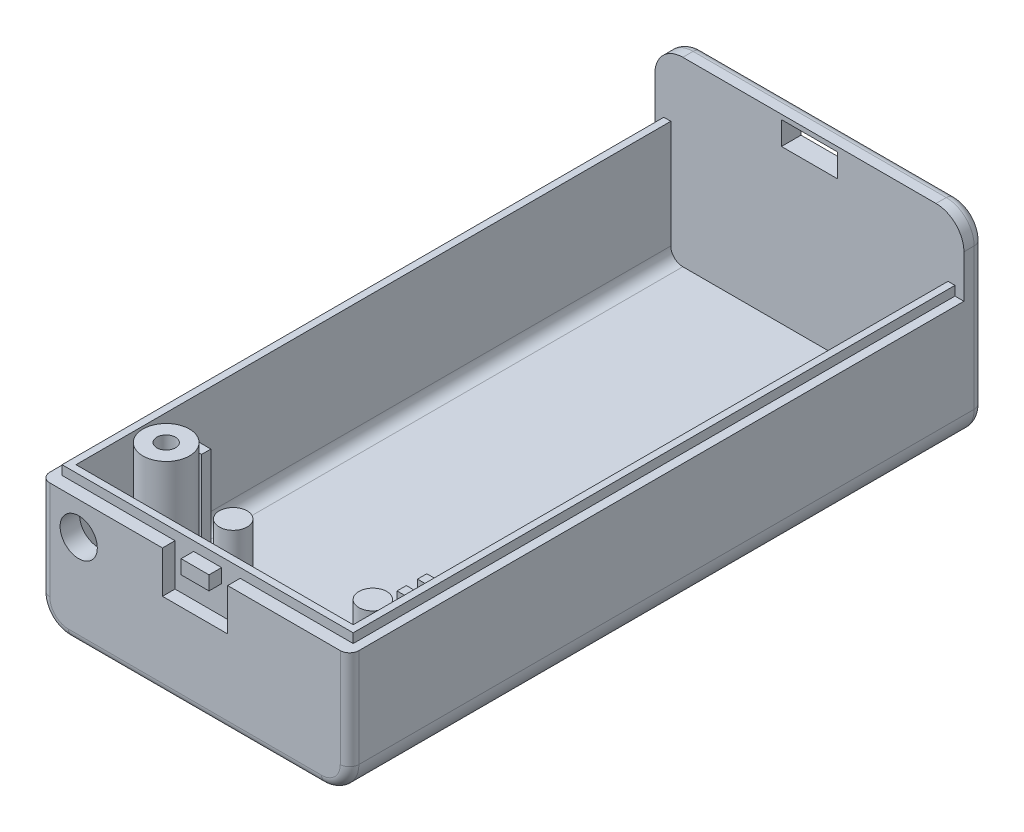
SolidWorks part; units mm, degrees
ref_plane "Plan de face" through (0, 0, 0) normal (0, 0, 1) x (1, 0, 0)
ref_plane "Plan de dessus" through (0, 0, 0) normal (0, 1, 0) x (1, 0, 0)
ref_plane "Plan de droite" through (0, 0, 0) normal (1, 0, 0) x (0, 0, -1)
sketch "Esquisse1" plane through (0, 0, 0) normal (0, 0, 1) x (1, 0, 0)
  line L0 (0, 15.2923) -> (0, -18.7385) construction
  line L1 (-13.6, -14.6) -> (13.6, -14.6)
  line L2 (-16.6, -11.6) -> (-16.6, 0)
  line L3 (16.6, -11.6) -> (16.6, 0)
  arc A0 (16.6, -11.6) -> (13.6, -14.6) centre (13.6, -11.6) cw
  arc A1 (-13.6, -14.6) -> (-16.6, -11.6) centre (-13.6, -11.6) cw
  point P3 (-16.6, -5.8)
  point P12 (16.6, -5.8)
  dimension "D3" = 3
  dimension "D1" = 16.6
  dimension "D2" = 14.6
  dimension "D4" = 16.6
extrude "Extru.-Mince1" add sketch "Esquisse1" along normal blind 32 and the other way blind 32 thin thin type one direction reverse wall 1.71
sketch "Esquisse2" plane through (0, 0, 32) normal (0, 0, 1) x (1, 0, 0)
  line L0 (16.6, -11.6) -> (16.6, 0) construction
  line L1 (-13.6, -14.6) -> (13.6, -14.6) construction
  line L2 (-16.6, 0) -> (-16.6, -11.6) construction
  line L3 (16.6, -11.6) -> (16.6, 0)
  line L4 (-13.6, -14.6) -> (13.6, -14.6)
  line L5 (-16.6, 0) -> (-16.6, -11.6)
  line L6 (-16.6, 0) -> (-3.5, 0)
  line L7 (0, 3.7553) -> (0, -16.7122) construction
  line L8 (-3.5, 0) -> (-3.5, -5.5)
  line L9 (-3.5, -5.5) -> (3.5, -5.5)
  line L10 (3.5, -5.5) -> (3.5, 0)
  line L11 (3.5, 0) -> (16.6, 0)
  arc A0 (13.6, -14.6) -> (16.6, -11.6) centre (13.6, -11.6) ccw construction
  arc A1 (-16.6, -11.6) -> (-13.6, -14.6) centre (-13.6, -11.6) ccw construction
  arc A2 (13.6, -14.6) -> (16.6, -11.6) centre (13.6, -11.6) ccw
  arc A3 (-16.6, -11.6) -> (-13.6, -14.6) centre (-13.6, -11.6) ccw
  point P13 (-3.5, -2.75)
  dimension "D1" = 7
  dimension "D2" = 5.5
extrude "Boss.-Extru.1" add sketch "Esquisse2" along normal blind 2 and the other way blind 0.1
sketch "Esquisse3" plane through (0, 0, -32) normal (0, 0, -1) x (-1, 0, 0)
  line L0 (-16.6, 3.6) -> (-16.6, -11.6)
  line L1 (-13.6, 6.6) -> (13.6, 6.6)
  line L2 (16.6, 3.6) -> (16.6, -11.6)
  line L3 (0, 9.8027) -> (0, -17.3044) construction
  line L5 (-3, 6.1) -> (3, 6.1)
  line L6 (-3, 6.1) -> (-3, 3.6)
  line L7 (-3, 3.6) -> (3, 3.6)
  line L8 (-13.6, -14.6) -> (13.6, -14.6)
  line L9 (13.6, -14.6) -> (-13.6, -14.6) construction
  line L24 (3, 6.1) -> (3, 3.6)
  arc A0 (13.6, 6.6) -> (16.6, 3.6) centre (13.6, 3.6) cw
  arc A1 (-16.6, 3.6) -> (-13.6, 6.6) centre (-13.6, 3.6) cw
  arc A2 (16.6, -11.6) -> (13.6, -14.6) centre (13.6, -11.6) cw
  arc A3 (-16.6, -11.6) -> (-13.6, -14.6) centre (-13.6, -11.6) ccw
  dimension "D6" = 3
  dimension "D1" = 3
  dimension "D2" = 21.2
  dimension "D3" = 6
  dimension "D4" = 2.5
  dimension "D5" = 0.5
  dimension "D7" = 33.2
extrude "Boss.-Extru.2" add sketch "Esquisse3" along normal blind 2.1
sketch "Esquisse4" plane through (0, 0, 31.9) normal (0, 0, -1) x (-1, 0, 0)
  line L1 (-3.5, 0) -> (3.5, 0)
  line L2 (-3.5, 0) -> (-3.5, -5.5)
  line L3 (-3.5, -5.5) -> (3.5, -5.5)
  line L4 (3.5, 0) -> (3.5, -5.5)
extrude "Boss.-Extru.3" add sketch "Esquisse4" against normal blind 0.75
sketch "Esquisse5" plane through (0, 0, 0) normal (0, 1, 0) x (1, 0, 0)
  line L0 (0, 36.8403) -> (0, -38.829) construction
  line L2 (-15.64, 32) -> (-15.64, -32.65)
  line L3 (-15.64, -32.65) -> (15.64, -32.65)
  line L4 (15.64, 32) -> (15.64, -32.65)
  line L5 (-14.89, 32) -> (-14.89, -31.9) construction
  line L6 (13.6, -31.9) -> (-13.6, -31.9) construction
  line L7 (-16.6, 32) -> (-14.89, 32) construction
  line L8 (-15.64, 32) -> (-17.2139, 32)
  line L9 (-17.2139, 32) -> (-17.2139, -40.0916)
  line L10 (-17.2139, -40.0916) -> (20.2258, -40.0916)
  line L11 (15.64, 32) -> (20.2258, 32)
  line L12 (20.2258, 32) -> (20.2258, -40.0916)
  dimension "D1" = 0.75
  dimension "D2" = 0.75
extrude "Enlèv. mat.-Extru.2" cut sketch "Esquisse5" against normal blind 1
fillet "Congé1" radius 1 13 edges at (-16.6, -6.3, 34) (-15.7213, -13.7213, 34) (0, -14.6, 34) (15.7213, -13.7213, 34) (16.6, -6.3, 34) (-15.7213, -13.7213, -34.1) (0, -14.6, -34.1) (15.7213, -13.7213, -34.1) (16.6, -4, -34.1) (15.7213, 5.7213, -34.1) (0, 6.6, -34.1) (-15.7213, 5.7213, -34.1) (-16.6, -4, -34.1)
ref_plane "Plan1" through (0, 0, 21.7) normal (0, 0, 1) x (1, 0, 0)
sketch "Esquisse6" plane through (0, 0, 21.7) normal (0, 0, 1) x (1, 0, 0)
  line L0 (-15.6, -1) -> (-15.6, -11.6) construction
  line L1 (-15.6, -2.5) -> (-11.6, -2.5)
  line L2 (-15.6, -2.5) -> (-15.6, -13.6)
  line L3 (-15.6, -13.6) -> (-11.6, -13.6)
  line L4 (-11.6, -2.5) -> (-11.6, -13.6)
  line L5 (-13.6, -13.6) -> (13.6, -13.6) construction
  line L6 (0, 8.3493) -> (0, -16.8305) construction
  line L7 (-3.5, -1) -> (-15.64, -1) construction
  line L8 (15.6, -13.6) -> (11.6, -13.6)
  line L9 (11.6, -2.5) -> (11.6, -13.6)
  line L10 (15.6, -2.5) -> (11.6, -2.5)
  line L11 (15.6, -2.5) -> (15.6, -13.6)
  dimension "D1" = 4
  dimension "D2" = 1.5
extrude "Boss.-Extru.4" add sketch "Esquisse6" against normal blind 1
pattern_linear "Répétition linéaire1" count 2 spacing 2.2 along (0, 0, 1) of "Boss.-Extru.4"
sketch "Esquisse7" plane through (0, -12.89, 0) normal (0, 1, 0) x (1, 0, 0)
  line L0 (0, 8.6423) -> (0, -38.4492) construction
  line L1 (-16.6, -33) -> (-16.6, 32) construction
  line L2 (-3.5, -34) -> (-15.6, -34) construction
  circle A0 centre (-9.6, -27.5) radius 2.5
  circle A1 centre (-9.6, -27.5) radius 1
  dimension "D1" = 5
  dimension "D2" = 2
  dimension "D3" = 7
  dimension "D4" = 6.5
extrude "Boss.-Extru.5" add sketch "Esquisse7" along normal blind 15.4
sketch "Esquisse8" plane through (0, -12.89, 0) normal (0, 1, 0) x (1, 0, 0)
  line L0 (-19.5582, -27.5) -> (14.7582, -27.5) construction
  line L1 (-3.5, -34) -> (-15.6, -34) construction
  line L2 (16.6, 32) -> (16.6, -33) construction
  circle A0 centre (12.6, -27.5) radius 1.5
  circle A1 centre (-2.4, -27.5) radius 1.5
  point P6 (-2.4, -27.5)
  dimension "D1" = 3
  dimension "D2" = 3
  dimension "D3" = 6.5
  dimension "D4" = 4
  dimension "D5" = 15
extrude "Boss.-Extru.6" add sketch "Esquisse8" along normal up to surface (11.89 mm away) up to face at (-12.4696, -1, 14.6439)
sketch "Esquisse9" plane through (0, -12.89, 0) normal (0, 1, 0) x (1, 0, 0)
  line L0 (-18.8936, -27.5) -> (19.9379, -27.5) construction
  line L1 (2.1, -25.625) -> (10.1, -25.625)
  line L2 (2.1, -25.625) -> (2.1, -29.375)
  line L3 (2.1, -29.375) -> (10.1, -29.375)
  line L4 (10.1, -25.625) -> (10.1, -29.375)
  line L5 (-3.5, -34) -> (-15.6, -34) construction
  line L6 (16.6, 32) -> (16.6, -33) construction
  dimension "D1" = 6.5
  dimension "D2" = 8
  dimension "D3" = 6.5
  dimension "D4" = 3.75
extrude "Enlèv. mat.-Extru.3" cut sketch "Esquisse9" against normal through all
sketch "Esquisse10" plane through (0, -14.6, 0) normal (0, -1, 0) x (1, 0, 0)
  text T0 "OFF-ON" font "Century Gothic" height 1.5
extrude "Boss.-Extru.7" add sketch "Esquisse10" along normal blind 0.1
sketch "Esquisse11" plane through (0, 0, 34) normal (0, 0, 1) x (1, 0, 0)
  circle A0 centre (-12.5, -4.5) radius 2
  dimension "D3" = 4
  dimension "D1" = 4.5
  dimension "D2" = 12.5
extrude "Enlèv. mat.-Extru.5" cut sketch "Esquisse11" against normal up to next
sketch "Esquisse12" plane through (0, 0, 32.65) normal (0, 0, 1) x (1, 0, 0)
  line L0 (0, 5.1244) -> (0, -17.1383) construction
  line L1 (-1.5, -1) -> (1.5, -1)
  line L2 (-1.5, -1) -> (-1.5, -2.5)
  line L3 (-1.5, -2.5) -> (1.5, -2.5)
  line L4 (1.5, -1) -> (1.5, -2.5)
  line L5 (15.6, -1) -> (3.5, -1) construction
  dimension "D1" = 3
  dimension "D2" = 1.5
extrude "Boss.-Extru.8" add sketch "Esquisse12" along normal up to surface (1.35 mm away) up to face at (-10.5, -4.5, 34)
